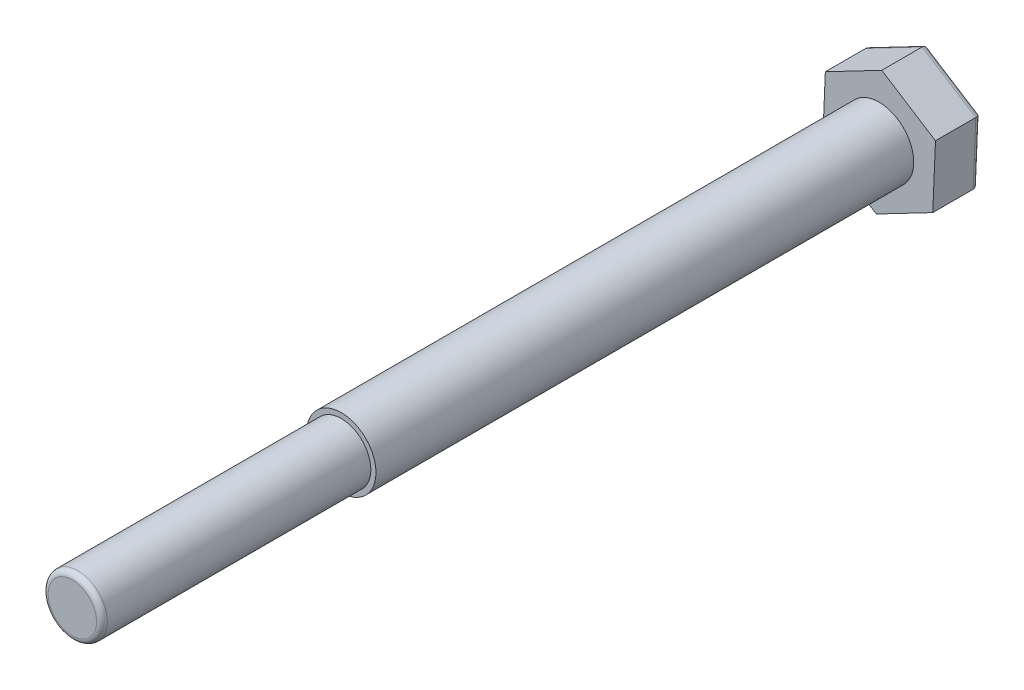
SolidWorks part; units mm, degrees
ref_plane "前视" through (0, 0, 0) normal (0, 0, 1) x (1, 0, 0)
ref_plane "上视" through (0, 0, 0) normal (0, 1, 0) x (1, 0, 0)
ref_plane "右视" through (0, 0, 0) normal (1, 0, 0) x (0, 0, -1)
sketch "草图1" plane through (0, 0, 0) normal (0, 0, 1) x (1, 0, 0)
  line L1 (20.9842, 10.9543) -> (1.0054, 23.65)
  line L2 (1.0054, 23.65) -> (-19.9788, 12.6957)
  line L3 (-19.9788, 12.6957) -> (-20.9842, -10.9543)
  line L4 (-20.9842, -10.9543) -> (-1.0054, -23.65)
  line L5 (-1.0054, -23.65) -> (19.9788, -12.6957)
  line L6 (19.9788, -12.6957) -> (20.9842, 10.9543)
  circle A0 centre (0, 0) radius 20.5 construction
  dimension "D1" = 47.3
  dimension "D2" = 41
extrude "基体-拉伸" add sketch "草图1" along normal blind 17
sketch "草图2" plane through (0, 0, 17) normal (0, 0, 1) x (1, 0, 0)
  circle A0 centre (0, 0) radius 12.9
  dimension "D1" = 25.8
extrude "凸台-拉伸1" add sketch "草图2" along normal blind 200
fillet "圆角3" radius 2 6 edges at (10.9948, 17.3021, 0) (-9.4867, 18.1729, 0) (-20.4815, 0.8707, 0) (-10.9948, -17.3021, 0) (9.4867, -18.1729, 0) (20.4815, -0.8707, 0)
sketch "草图3" plane through (0, 0, 217) normal (0, 0, 1) x (1, 0, 0)
  circle A0 centre (0, 0) radius 11
  dimension "D1" = 22
extrude "凸台-拉伸2" add sketch "草图3" along normal blind 100
fillet "圆角4" radius 2 1 edges at (11, 0, 317)
